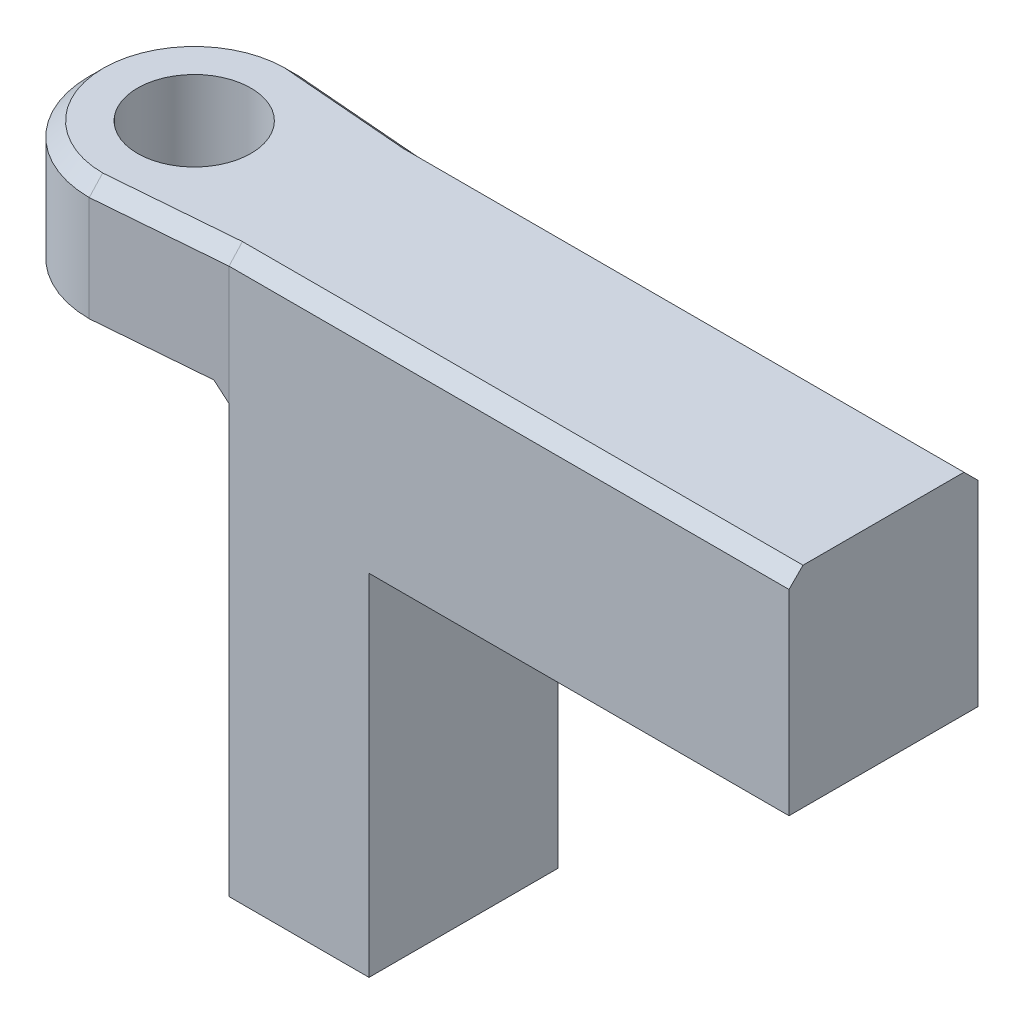
SolidWorks part; units mm, degrees
note: The reader was unsure of these and kept them because the rebuilt part matched: shared geometry of "Sketch2<3>", "Sketch2<4>".
ref_plane "Front Plane" through (0, 0, 0) normal (0, 0, 1) x (1, 0, 0)
ref_plane "Top Plane" through (0, 0, 0) normal (0, 1, 0) x (1, 0, 0)
ref_plane "Right Plane" through (0, 0, 0) normal (1, 0, 0) x (0, 0, -1)
sketch "Sketch2" plane through (0, 0, 0) normal (0, 1, 0) x (1, 0, 0)
  line L0 (0, 15) -> (18.471, 13.5)
  line L1 (18.471, 13.5) -> (38.471, 13.5)
  line L2 (38.471, 13.5) -> (38.471, -13.5)
  line L3 (38.471, -13.5) -> (18.471, -13.5)
  line L4 (18.471, -13.5) -> (0, -15)
  line L5 (18.471, 13.5) -> (18.471, -13.5)
  circle A0 centre (0, 0) radius 8.1
  circle A1 centre (0, 0) radius 15
  circle A2 centre (0, 0) radius 5
  dimension "D1" = 16.2
  dimension "D2" = 30
  dimension "D3" = 10
  dimension "D4" = 27
  dimension "D5" = 20
extrude "Boss-Extrude1" add sketch "Sketch2" along normal blind 15 contours A1 A0 | A1 L4 L5 L0
extrude "Boss-Extrude2" add sketch "Sketch2<3>" against normal blind 2 contours A0 A2 | A1 A0 | A1 L4 L5 L0
sketch "Sketch2<3>" plane through (0, 0, 0) normal (0, 1, 0) x (1, 0, 0) same geometry as "Sketch2"
sketch "Sketch3" plane through (0, -2, 0) normal (0, -1, 0) x (1, 0, 0)
  circle A0 centre (0, -10) radius 1.5
  circle A1 centre (0, 10) radius 1.5
  circle A2 centre (0, 0) radius 5 construction
  dimension "D3" = 3
  dimension "D1" = 20
  dimension "D2" = 10
extrude "Cut-Extrude1" cut sketch "Sketch3" against normal blind 10
extrude "Boss-Extrude3" add sketch "Sketch2<4>" along normal up to surface and the other way blind 65 contours A1 L4 L3 L2 L1 L0
sketch "Sketch2<4>" plane through (0, 0, 0) normal (0, 1, 0) x (1, 0, 0) same geometry as "Sketch2"
chamfer "Chamfer3" distance 2 angle 45 1 edges at (18.471, -2, 0)
sketch "Sketch4" plane through (38.471, 0, 0) normal (1, 0, 0) x (0, 0, -1)
  line L1 (-13.5, -15) -> (13.5, -15)
  line L2 (-13.5, -15) -> (-13.5, 15)
  line L3 (-13.5, 15) -> (13.5, 15)
  line L4 (13.5, -15) -> (13.5, 15)
  line L5 (-13.5, -15) -> (13.5, 15) construction
  line L6 (-13.5, 15) -> (13.5, -15) construction
  point P0 (0, 0)
extrude "Boss-Extrude4" add sketch "Sketch4" along normal blind 60
chamfer "Chamfer6" distance 2 angle 45 3 edges at (9.2355, 15, -14.25) (9.2355, 15, 14.25) (-15, 15, 0)
sketch "Sketch5" plane through (98.471, 0, 0) normal (1, 0, 0) x (0, 0, -1)
